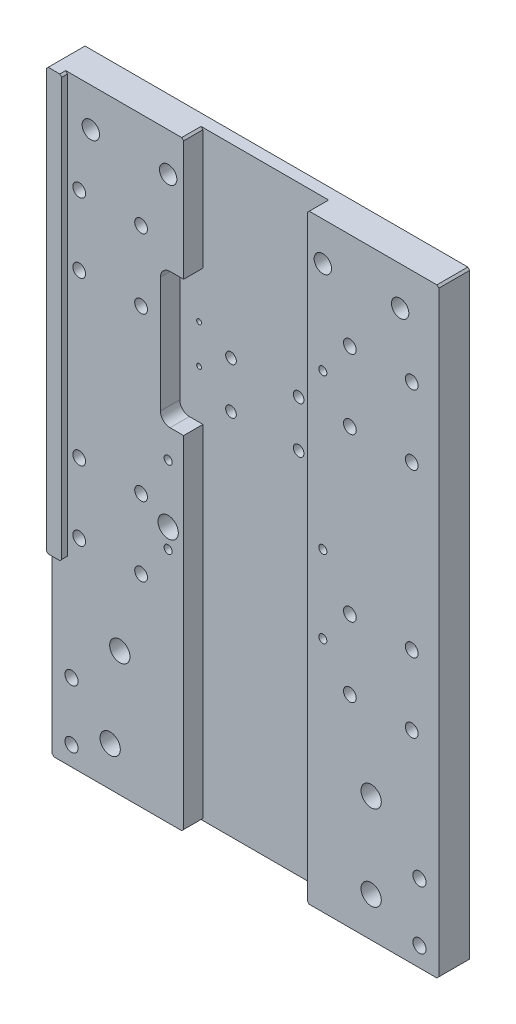
SolidWorks part; units mm, degrees
material "6061-T6 (SS)"
ref_plane "Front Plane" through (0, 0, 0) normal (0, 0, 1) x (1, 0, 0)
ref_plane "Top Plane" through (0, 0, 0) normal (0, 1, 0) x (1, 0, 0)
ref_plane "Right Plane" through (0, 0, 0) normal (1, 0, 0) x (0, 0, -1)
sketch "Sketch1" plane through (0, 0, 0) normal (0, 0, 1) x (1, 0, 0)
  line L0 (0, -10.4775) -> (0, 10.4775) construction
  line L1 (-70, 60) -> (70, 60) construction
  line L2 (-70, 60) -> (-70, -60) construction
  line L3 (-70, -60) -> (70, -60) construction
  line L4 (70, 60) -> (70, -60) construction
  line L5 (-70, 60) -> (70, -60) construction
  line L6 (-70, -60) -> (70, 60) construction
  line L7 (-86, 78) -> (-54, 78) construction
  line L8 (-86, 78) -> (-86, 42) construction
  line L9 (-86, 42) -> (-54, 42) construction
  line L10 (-54, 78) -> (-54, 42) construction
  line L11 (-86, 78) -> (-54, 42) construction
  line L12 (-86, 42) -> (-54, 78) construction
  line L13 (-100, 128) -> (100, 128)
  line L14 (-100, 128) -> (-100, -182.5)
  line L15 (-100, -182.5) -> (100, -182.5)
  line L16 (100, 128) -> (100, -182.5)
  line L17 (-100, -97.5) -> (100, -97.5) construction
  line L18 (-100, 88) -> (100, 88) construction
  line L19 (54, -42) -> (86, -42) construction
  line L20 (54, -42) -> (54, -78) construction
  line L21 (54, -78) -> (86, -78) construction
  line L22 (86, -42) -> (86, -78) construction
  line L23 (54, -42) -> (86, -78) construction
  line L24 (54, -78) -> (86, -42) construction
  line L25 (35.5, -12.5) -> (54.5, -12.5) construction
  line L26 (-17.5, 32) -> (17.5, 32) construction
  line L27 (-17.5, 32) -> (-17.5, 8) construction
  line L28 (-17.5, 8) -> (17.5, 8) construction
  line L29 (17.5, 32) -> (17.5, 8) construction
  line L30 (-17.5, 32) -> (17.5, 8) construction
  line L31 (-17.5, 8) -> (17.5, 32) construction
  line L32 (-100, -97.5) -> (100, -182.5) construction
  point P0 (0, 0)
  point P14 (0, -182.5)
  point P23 (0, 20)
  point P33 (0, -140)
  point P35 (45, -12.5)
  dimension "D1" = 120
  dimension "D2" = 140
  dimension "D3" = 36
  dimension "D4" = 32
  dimension "D5" = 85
  dimension "D6" = 19.5
  dimension "D7" = 40
  dimension "D8" = 10
  dimension "D9" = 200
  dimension "D10" = 24
  dimension "D11" = 35
  dimension "D12" = 20
  dimension "D13" = 19
  dimension "D14" = 45
  dimension "D15" = 47.5
  dimension "D16" = 140
  dimension "D17" = 310.5
extrude "Boss-Extrude1" add sketch "Sketch1" along normal blind 19.05
sketch "Sketch2" plane through (0, 0, 19.05) normal (0, 0, 1) x (1, 0, 0)
  line L0 (100, 128) -> (-100, 128) construction
  line L1 (-92, 128) -> (100, 128)
  line L2 (-92, 128) -> (-92, -90)
  line L3 (-100, -182.5) -> (100, -182.5)
  line L4 (100, 128) -> (100, -182.5)
  line L5 (-92, -90) -> (-100, -90)
  line L6 (-100, 128) -> (-100, -182.5) construction
  line L7 (-70, 60) -> (-70, -60) construction
  line L8 (-100, -90) -> (-100, -182.5)
  line L9 (-70, -60) -> (70, -60) construction
  dimension "D1" = 22
  dimension "D2" = 30
extrude "Cut-Extrude1" cut sketch "Sketch2" against normal offset from surface (3.05 mm away) 16 up to face at (0, -27.25, 0)
sketch "Sketch3" plane through (0, 0, 16) normal (0, 0, 1) x (1, 0, 0)
  line L0 (-100, 128) -> (100, 128) construction
  line L1 (-32, 128) -> (32, 128)
  line L2 (-32, 128) -> (-32, 65)
  line L3 (-32, -182.5) -> (32, -182.5)
  line L4 (32, 128) -> (32, -182.5)
  line L5 (-100, -182.5) -> (100, -182.5) construction
  line L6 (0, -10.4775) -> (0, 10.4775) construction
  line L7 (-32, 65) -> (-39, 65)
  line L8 (-44, 60) -> (-44, 0)
  line L9 (-39, -5) -> (-32, -5)
  line L10 (-32, -5) -> (-32, -182.5)
  line L12 (-34, 40) -> (-34, 20) construction
  line L13 (-44, 30) -> (-34, 30) construction
  arc A0 (-44, 0) -> (-39, -5) centre (-39, 0) ccw
  arc A1 (-39, 65) -> (-44, 60) centre (-39, 60) ccw
  point P8 (0, -182.5)
  point P20 (-44, -5)
  point P23 (-44, 65)
  dimension "D4" = 5
  dimension "D1" = 64
  dimension "D2" = 34
  dimension "D3" = 70
  dimension "D5" = 20
  dimension "D6" = 10
  dimension "D7" = 30
extrude "Cut-Extrude2" cut sketch "Sketch3" against normal blind 10
hole_wizard "M6 Clearance Hole1" positions "Sketch4" profile "Sketch5" hole size "M6" standard "ANSI Metric" end condition up to next
sketch "Sketch4" plane through (0, 0, 16) normal (0, 0, 1) x (1, 0, 0)
  point P0 (54, -42)
  point P3 (86, -42)
  point P6 (86, -78)
  point P9 (54, -78)
sketch "Sketch5" plane through (54, -42, 16) normal (1, 0, 0) x (0, -1, 0)
  line L0 (0, 0) -> (0, 16)
  line L1 (0, 16) -> (3.3, 16)
  line L2 (3.3, 16) -> (3.3, 0)
  line L5 (3.3, 0) -> (0, 0)
  line L11 (0, -6.35) -> (0, 107.95) construction
  dimension "Thru Hole Dia." = 6.6
  dimension "Thru Hole Depth" = 16
mirror "Mirror1" about plane through (0, 0, 0) normal (0, 1, 0) of "M6 Clearance Hole1"
hole_wizard "M8 Clearance Hole1" positions "Sketch13" profile "Sketch14" hole size "M8" standard "ANSI Metric" end condition up to next
sketch "Sketch13" plane through (0, 0, 16) normal (0, 0, 1) x (1, 0, 0)
  line L0 (40, 108) -> (80, 108)
  line L2 (-100, 88) -> (100, 88) construction
  line L3 (0, -10.4775) -> (0, 10.4775) construction
  point P1 (40, 108)
  point P2 (80, 108)
  dimension "D1" = 20
  dimension "D2" = 40
  dimension "D3" = 40
sketch "Sketch14" plane through (40, 108, 16) normal (1, 0, 0) x (0, -1, 0)
  line L0 (0, 0) -> (0, 16)
  line L1 (0, 16) -> (4.5, 16)
  line L2 (4.5, 16) -> (4.5, 0)
  line L5 (4.5, 0) -> (0, 0)
  line L11 (0, -6.35) -> (0, 107.95) construction
  dimension "Thru Hole Dia." = 9
  dimension "Thru Hole Depth" = 16
hole_wizard "M5x0.8 Tapped Hole1" positions "Sketch15" profile "Sketch16" tap size "M5x0.8" standard "ANSI Metric" end condition up to next
sketch "Sketch15" plane through (0, 0, 16) normal (0, 0, 1) x (1, 0, 0)
  line L0 (40, 60) -> (40, -20)
  line L1 (40, -20) -> (40, -60)
  line L3 (-70, -60) -> (70, -60) construction
  line L4 (-70, 60) -> (70, 60) construction
  point P0 (40, 60)
  point P1 (40, -20)
  point P3 (40, -60)
  dimension "D1" = 40
  dimension "D2" = 80
  dimension "D3" = 40
sketch "Sketch16" plane through (40, 60, 16) normal (1, 0, 0) x (0, -1, 0)
  line L0 (0, 0) -> (0, 16)
  line L1 (0, 16) -> (2.1, 16)
  line L2 (2.1, 16) -> (2.1, 0)
  line L5 (2.1, 0) -> (0, 0)
  line L11 (0, -6.35) -> (0, 107.95) construction
  dimension "Thru Tap Drill Dia." = 4.2
  dimension "Thru Tap Drill Depth" = 16
cosmetic thread "Hole Thread5" parameters "D2"=5
cosmetic thread "Hole Thread6" parameters "D2"=5
cosmetic thread "Hole Thread7" parameters "D2"=5
mirror "Mirror2" about plane through (0, 0, 0) normal (1, 0, 0) of "M5x0.8 Tapped Hole1", "M8 Clearance Hole1", "Mirror1"
cosmetic thread "Hole Thread8" parameters "D2"=5
cosmetic thread "Hole Thread9" parameters "D2"=5
cosmetic thread "Hole Thread10" parameters "D2"=5
hole_wizard "M5 Clearance Hole1" positions "Sketch11" profile "Sketch12" hole size "M5" standard "ANSI Metric" end condition up to next
sketch "Sketch11" plane through (0, 0, 6) normal (0, 0, 1) x (1, 0, 0)
  point P0 (-17.5, 32)
  point P3 (17.5, 32)
  point P6 (17.5, 8)
  point P9 (-17.5, 8)
sketch "Sketch12" plane through (-17.5, 32, 6) normal (1, 0, 0) x (0, -1, 0)
  line L0 (0, 0) -> (0, 6)
  line L1 (0, 6) -> (2.75, 6)
  line L2 (2.75, 6) -> (2.75, 0)
  line L5 (2.75, 0) -> (0, 0)
  line L11 (0, -6.35) -> (0, 107.95) construction
  dimension "Thru Hole Dia." = 5.5
  dimension "Thru Hole Depth" = 6
hole_wizard "M12x1.5 Tapped Hole1" positions "Sketch17" profile "Sketch18" tap size "M12x1.5" standard "ANSI Metric" end condition up to next
sketch "Sketch17" plane through (0, 0, 16) normal (0, 0, 1) x (1, 0, 0)
  line L1 (-65, -118) -> (65, -118)
  line L2 (-65, -118) -> (-65, -162)
  line L3 (-65, -162) -> (65, -162)
  line L4 (65, -118) -> (65, -162)
  line L5 (-65, -118) -> (65, -162) construction
  line L6 (-65, -162) -> (65, -118) construction
  line L7 (-65, -162) -> (-70, -162)
  point P2 (65, -162)
  point P63 (-65, -118)
  point P65 (65, -118)
  point P72 (-70, -162)
  dimension "D1" = 44
  dimension "D2" = 130
  dimension "D3" = 5
sketch "Sketch18" plane through (65, -162, 16) normal (1, 0, 0) x (0, -1, 0)
  line L0 (0, 0) -> (0, 16)
  line L1 (0, 16) -> (5.25, 16)
  line L2 (5.25, 16) -> (5.25, 0)
  line L5 (5.25, 0) -> (0, 0)
  line L11 (0, -6.35) -> (0, 107.95) construction
  dimension "Thru Tap Drill Dia." = 10.5
  dimension "Thru Tap Drill Depth" = 16
cosmetic thread "Hole Thread11" parameters "D2"=12
cosmetic thread "Hole Thread12" parameters "D2"=12
cosmetic thread "Hole Thread13" parameters "D2"=12
cosmetic thread "Hole Thread14" parameters "D2"=12
hole_wizard "M8x1.25 Tapped Hole1" positions "Sketch20" profile "Sketch21" tap size "M8x1.25" standard "ANSI Metric" end condition up to next
sketch "Sketch20" plane through (0, 0, 0) normal (0, 0, -1) x (-1, 0, 0)
  line L1 (-90, -142.5) -> (90, -142.5)
  line L2 (-90, -142.5) -> (-90, -172.5)
  line L3 (-90, -172.5) -> (90, -172.5)
  line L4 (90, -142.5) -> (90, -172.5)
  line L5 (0, 10.4775) -> (0, -10.4775) construction
  line L6 (100, -182.5) -> (-100, -182.5) construction
  point P1 (-90, -142.5)
  point P2 (90, -172.5)
  point P205 (-90, -172.5)
  point P206 (90, -142.5)
  point P208 (0, -142.5)
  dimension "D1" = 180
  dimension "D2" = 10
  dimension "D3" = 30
sketch "Sketch21" plane through (90, -142.5, 0) normal (1, 0, 0) x (0, 1, 0)
  line L0 (0, 0) -> (0, 16)
  line L1 (0, 16) -> (3.4, 16)
  line L2 (3.4, 16) -> (3.4, 0)
  line L5 (3.4, 0) -> (0, 0)
  line L11 (0, -6.35) -> (0, 107.95) construction
  dimension "Thru Tap Drill Dia." = 6.8
  dimension "Thru Tap Drill Depth" = 16
cosmetic thread "Hole Thread15" parameters "D2"=8
cosmetic thread "Hole Thread16" parameters "D2"=8
cosmetic thread "Hole Thread17" parameters "D2"=8
cosmetic thread "Hole Thread18" parameters "D2"=8
hole_wizard "M3x0.5 Tapped Hole1" positions "Sketch22" profile "Sketch23" tap size "M3x0.5" standard "ANSI Metric" end condition up to next
sketch "Sketch22" plane through (0, 0, 6) normal (0, 0, 1) x (1, 0, 0)
  point P1 (-34, 40)
  point P2 (-34, 20)
  point P14 (-34, 20)
  point P16 (-34, 0)
sketch "Sketch23" plane through (-34, 40, 6) normal (1, 0, 0) x (0, -1, 0)
  line L0 (0, 0) -> (0, 6)
  line L1 (0, 6) -> (1.25, 6)
  line L2 (1.25, 6) -> (1.25, 0)
  line L5 (1.25, 0) -> (0, 0)
  line L11 (0, -6.35) -> (0, 107.95) construction
  dimension "Thru Tap Drill Dia." = 2.5
  dimension "Thru Tap Drill Depth" = 6
cosmetic thread "Hole Thread19" parameters "D2"=3
cosmetic thread "Hole Thread20" parameters "D2"=3
hole_wizard "M12x1.5 Tapped Hole2" positions "Sketch24" profile "Sketch25" tap size "M12x1.5" standard "ANSI Metric" end condition up to next
sketch "Sketch24" plane through (0, 0, 16) normal (0, 0, 1) x (1, 0, 0)
  line L0 (0, -10.4775) -> (0, 10.4775) construction
  point P0 (-40, -50)
  dimension "D1" = 40
  dimension "D2" = 50
sketch "Sketch25" plane through (-40, -50, 16) normal (1, 0, 0) x (0, -1, 0)
  line L0 (0, 0) -> (0, 16)
  line L1 (0, 16) -> (5.25, 16)
  line L2 (5.25, 16) -> (5.25, 0)
  line L5 (5.25, 0) -> (0, 0)
  line L11 (0, -6.35) -> (0, 107.95) construction
  dimension "Thru Tap Drill Dia." = 10.5
  dimension "Thru Tap Drill Depth" = 16
cosmetic thread "Hole Thread21" parameters "D2"=12
chamfer "Chamfer1" distance 1 11 edges at (100, 128, 8) (32, 128, 11) (-32, 128, 11) (-92, 128, 17.525) (-100, 128, 9.525) (32, -182.5, 11) (100, -182.5, 8) (-100, -182.5, 8) (-100, -90, 17.525) (-92, -90, 17.525) (-32, -182.5, 11)
